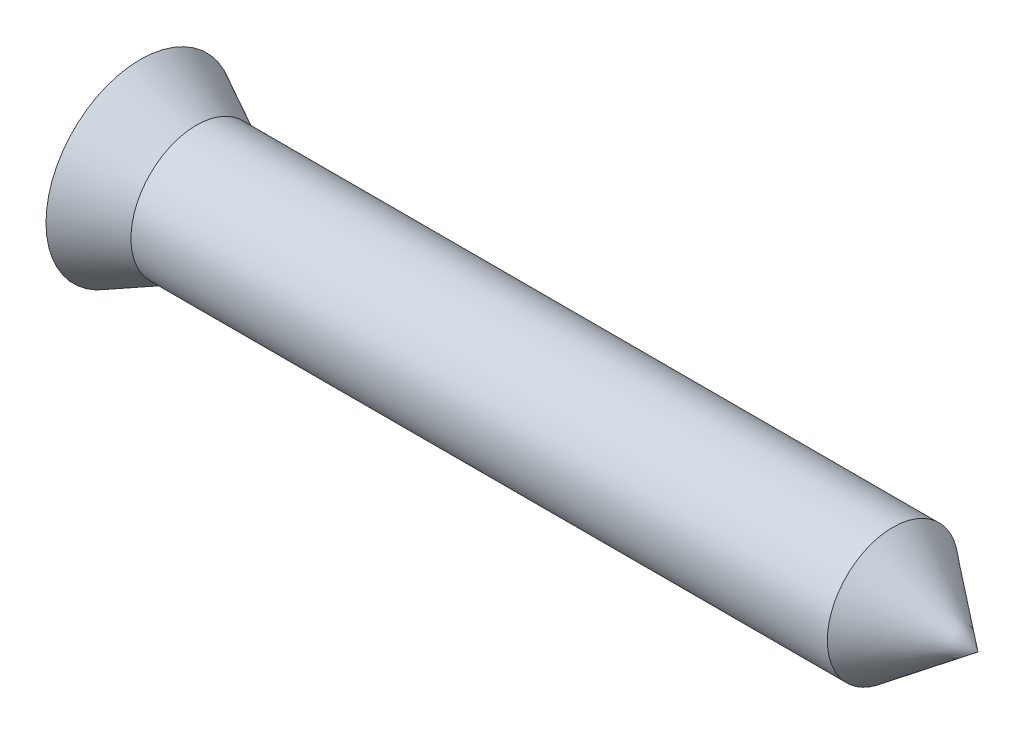
SolidWorks part; units mm, degrees
ref_plane "Front Plane" through (0, 0, 0) normal (0, 0, 1) x (1, 0, 0)
ref_plane "Top Plane" through (0, 0, 0) normal (0, 1, 0) x (1, 0, 0)
ref_plane "Right Plane" through (0, 0, 0) normal (1, 0, 0) x (0, 0, -1)
sketch "Sketch1" plane through (0, 0, 0) normal (0, 0, 1) x (1, 0, 0)
  line L0 (0, 0) -> (0, 2.8575)
  line L1 (0, -55) -> (0, 55) construction
  line L2 (0, 2.8575) -> (1.7018, 1.9844)
  line L3 (1.7018, 1.9844) -> (22.8173, 1.9844)
  line L4 (22.8173, 1.9844) -> (25.4, 0)
  line L5 (55, 0) -> (-55, 0) construction
  line L6 (25.4, 0) -> (0, 0)
  dimension "D1" = 25.4
  dimension "D2" = 1.7018
  dimension "D3" = 1.9844
  dimension "D4" = 2.8575
revolve "Revolve1" add sketch "Sketch1" angle 360 about L6
sketch "Sketch2" plane through (0, 0, 0) normal (1, 0, 0) x (0, 0, -1)
  line L0 (1.7874, 0.5646) -> (0.6805, 0.5646)
  line L1 (0.4265, 0.8186) -> (0.4265, 1.825)
  line L2 (0.1725, 2.079) -> (-0.1478, 2.079)
  line L3 (-0.4018, 1.825) -> (-0.4018, 0.8186)
  line L4 (-0.6558, 0.5646) -> (-1.93, 0.5646)
  line L5 (-2.184, 0.3106) -> (-2.184, -0.0023)
  line L6 (-1.93, -0.2563) -> (-0.6558, -0.2563)
  line L7 (-0.4018, -0.5103) -> (-0.4018, -1.9007)
  line L8 (-0.1478, -2.1547) -> (0.2562, -2.1547)
  line L9 (0.5102, -1.9007) -> (0.5102, -0.5261)
  line L10 (0.7642, -0.2721) -> (1.7874, -0.2721)
  line L11 (2.0414, -0.0181) -> (2.0414, 0.3106)
  arc A0 (0.5102, -0.5261) -> (0.7642, -0.2721) centre (0.7642, -0.5261) cw
  arc A1 (-0.6558, -0.2563) -> (-0.4018, -0.5103) centre (-0.6558, -0.5103) cw
  arc A2 (-0.4018, 0.8186) -> (-0.6558, 0.5646) centre (-0.6558, 0.8186) cw
  arc A3 (0.6805, 0.5646) -> (0.4265, 0.8186) centre (0.6805, 0.8186) cw
  arc A4 (1.7874, 0.5646) -> (2.0414, 0.3106) centre (1.7874, 0.3106) cw
  arc A5 (1.7874, -0.2721) -> (2.0414, -0.0181) centre (1.7874, -0.0181) ccw
  arc A6 (0.2562, -2.1547) -> (0.5102, -1.9007) centre (0.2562, -1.9007) ccw
  arc A7 (-0.4018, -1.9007) -> (-0.1478, -2.1547) centre (-0.1478, -1.9007) ccw
  arc A8 (-2.184, -0.0023) -> (-1.93, -0.2563) centre (-1.93, -0.0023) ccw
  arc A9 (-1.93, 0.5646) -> (-2.184, 0.3106) centre (-1.93, 0.3106) ccw
  arc A10 (-0.1478, 2.079) -> (-0.4018, 1.825) centre (-0.1478, 1.825) ccw
  arc A11 (0.4265, 1.825) -> (0.1725, 2.079) centre (0.1725, 1.825) ccw
  dimension "D1" = 0.254
extrude "Cut-Extrude2" cut sketch "Sketch2" along normal blind 0.254
ref_axis "Axis1" through (-1.27, 0, 0) along (1, 0, 0)
ref_plane "Plane1" through (25.4, 0, 0) normal (1, 0, 0) x (0, 0, -1)
